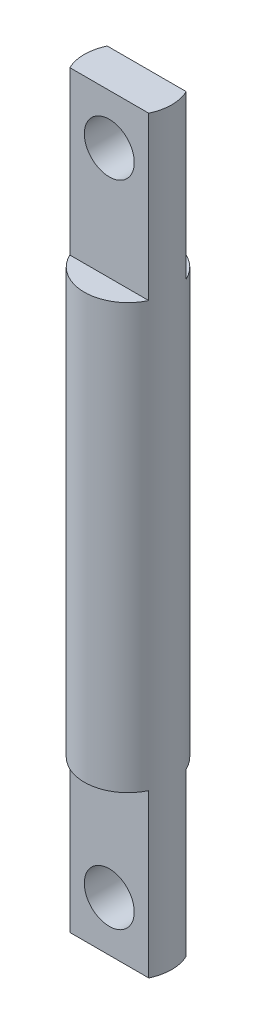
SolidWorks part; units mm, degrees
ref_plane "前视基准面" through (0, 0, 0) normal (0, 0, 1) x (1, 0, 0)
ref_plane "上视基准面" through (0, 0, 0) normal (0, 1, 0) x (1, 0, 0)
ref_plane "右视基准面" through (0, 0, 0) normal (1, 0, 0) x (0, 0, -1)
sketch "草图1" plane through (0, 0, 0) normal (0, 1, 0) x (1, 0, 0)
  circle A0 centre (0, 0) radius 3.5
  dimension "D1" = 7
extrude "凸台-拉伸1" add sketch "草图1" along normal blind 17 and the other way blind 17
sketch "草图2" plane through (0, -17, 0) normal (0, -1, 0) x (1, 0, 0)
  line L0 (-3.1623, 1.5) -> (3.1623, 1.5)
  line L1 (-3.1623, -1.5) -> (3.1623, -1.5)
  circle A0 centre (0, 0) radius 3.5 construction
  arc A1 (3.1623, 1.5) -> (3.1623, -1.5) centre (0, 0) cw
  arc A2 (3.1623, -1.5) -> (3.1623, 1.5) centre (0, 0) ccw
  arc A3 (-3.1623, 1.5) -> (-3.1623, -1.5) centre (0, 0) ccw
  circle M3 centre (0, 0) radius 3.5
  dimension "D1" = 3
extrude "凸台-拉伸2" add sketch "草图2" along normal blind 13 contours L1 L0 M3 region at (0, -17, 0)
sketch "草图5" plane through (0, 0, -1.5) normal (0, 0, -1) x (-1, 0, 0)
  line L0 (0, -17) -> (0, -30) construction
  line L1 (3.1623, -17) -> (-3.1623, -17) construction
  line L2 (3.1623, -30) -> (-3.1623, -30) construction
  circle A0 centre (0, -26) radius 2
  dimension "D2" = 4
  dimension "D1" = 9
extrude "切除-拉伸1" cut sketch "草图5" against normal up to next
mirror "镜向2" about plane through (0, 0, 0) normal (0, 1, 0) of "凸台-拉伸2", "切除-拉伸1"
